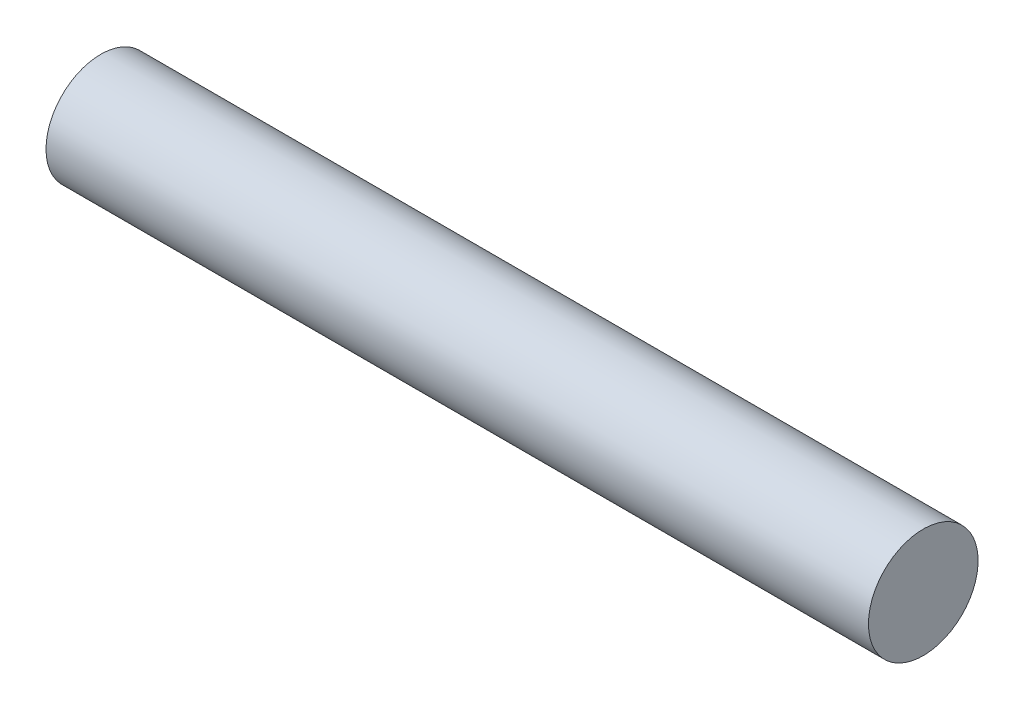
SolidWorks part; units mm, degrees
material "6061 Alloy"
ref_plane "Front Plane" through (0, 0, 0) normal (0, 0, 1) x (1, 0, 0)
ref_plane "Top Plane" through (0, 0, 0) normal (0, 1, 0) x (1, 0, 0)
ref_plane "Right Plane" through (0, 0, 0) normal (1, 0, 0) x (0, 0, -1)
sketch "Sketch1" plane through (0, 0, 0) normal (0, 0, 1) x (1, 0, 0)
  line L0 (-27.0684, 0) -> (28.7984, 0) construction
  line L1 (57.15, 7.62) -> (-57.15, 7.62)
  line L2 (-57.15, 7.62) -> (-57.15, 0)
  line L3 (57.15, 7.62) -> (57.15, 0)
  line L4 (57.15, 0) -> (-57.15, 0)
  point P6 (0, 7.62)
  dimension "D1" = 114.3
  dimension "D2" = 7.62
  dimension "D3" = 7.62
revolve "Revolve10" add sketch "Sketch1" angle 360 about L0
